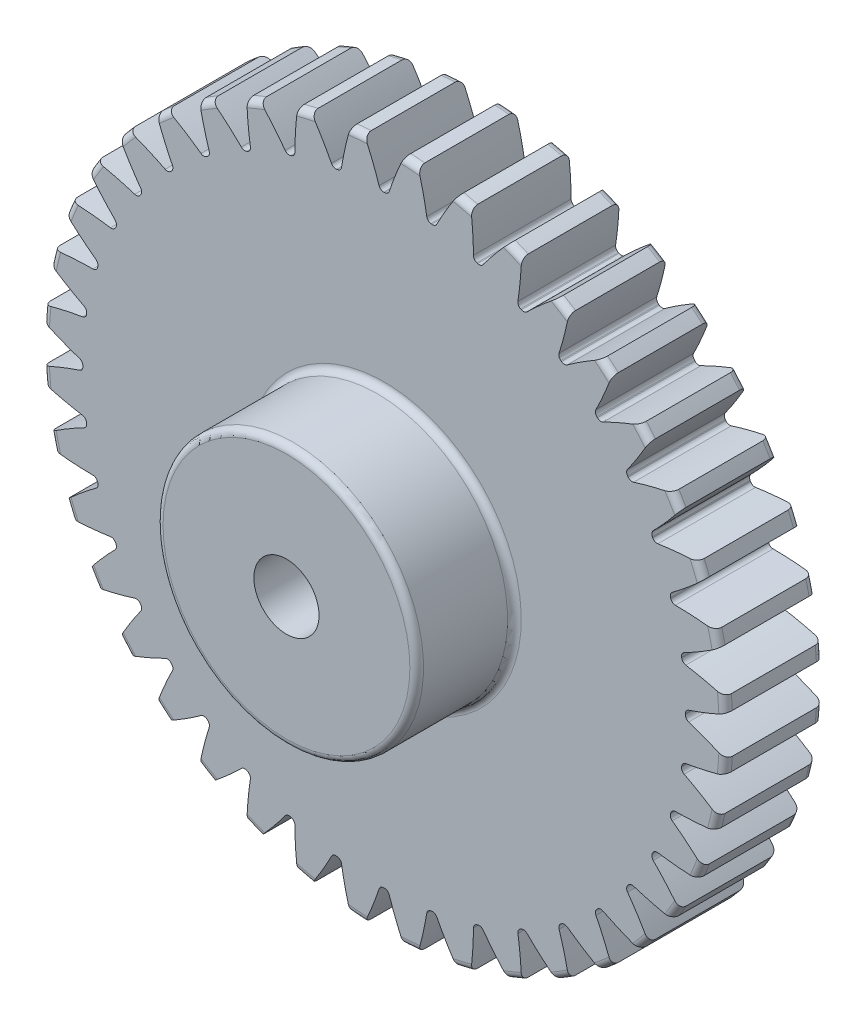
SolidWorks part; units mm, degrees
ref_plane "Front Plane" through (0, 0, 0) normal (0, 0, 1) x (1, 0, 0)
ref_plane "Top Plane" through (0, 0, 0) normal (0, 1, 0) x (1, 0, 0)
ref_plane "Right Plane" through (0, 0, 0) normal (1, 0, 0) x (0, 0, -1)
sketch "Sketch1" plane through (0, 0, 0) normal (0, 0, 1) x (1, 0, 0)
  line L0 (-508, 0) -> (508, 0) construction
  circle A0 centre (0, 0) radius 21 construction
  circle A1 centre (0, 0) radius 20 construction
  circle A2 centre (0, 0) radius 18.5 construction
  circle A3 centre (0, 0) radius 8 construction
  circle A4 centre (0, 0) radius 4 construction
  dimension "D2" = 1
  dimension "D3" = 2.5
  dimension "D1" = 2.5
sketch "Sketch2" plane through (0, 0, 0) normal (1, 0, 0) x (0, 0, -1)
  line L0 (0, 0) -> (-6, 0) construction
  line L1 (-6, 0) -> (-12, 0) construction
  dimension "Overall Width" = 12
  dimension "Face Width" = 6
sketch "Sketch4" plane through (0, 0, 0) normal (1, 0, 0) x (0, 0, -1)
  line L0 (-12, 4) -> (-12, 8)
  line L1 (-12, 8) -> (-6, 8)
  line L2 (-6, 8) -> (-6, 21)
  line L3 (-6, 21) -> (0, 21)
  line L4 (0, 21) -> (0, 4)
  line L5 (-6, 8) -> (-6, 0) construction
  line L6 (0, 21) -> (0, -21) construction
  line L7 (-6, 8) -> (0, 8) construction
  line L12 (-12, 4) -> (0, 4)
revolve "Revolve1" add sketch "Sketch4" angle 360 about L1
fillet "Fillet2" radius 0.42 4 edges at (0, 8, 12) (0, 8, 6) (0, 21, 6) (0, 21, 0)
sketch "Sketch7" plane through (0, 0, 6) normal (0, 0, 1) x (1, 0, 0)
  line L0 (0, 0) -> (0, 21) construction
  line L1 (0.7852, 19.9846) -> (1.1869, 20.9664) construction
  line L3 (1.6476, 20.9353) -> (1.5692, 19.9383) construction
  line L4 (1.5692, 19.9383) -> (1.4515, 18.443) construction
  line L5 (0, 0) -> (1.4515, 18.443) construction
  line L6 (0.7852, 19.9846) -> (0, 0) construction
  line L7 (0.7852, 19.9846) -> (0.8245, 20.9838) construction
  line L8 (0.7852, 19.9846) -> (0, 0) construction
  circle A0 centre (0, 0) radius 21 construction
  arc A1 (-0.027, 18.5) -> (0.027, 18.5) centre (0, 0) cw
  circle A2 centre (0, 0) radius 18.5 construction
  arc A3 (-0.7852, 19.9846) -> (0.7852, 19.9846) centre (0, 0) cw construction
  circle A4 centre (0, 0) radius 20 construction
  arc A5 (2.0774, 20.897) -> (1.2172, 20.9647) centre (0, 0) ccw construction
  arc A6 (0.7852, 19.9846) -> (2.3507, 19.8614) centre (0, 0) cw construction
  arc A7 (-1.2172, 20.9647) -> (1.2172, 20.9647) centre (0, 0) cw
  arc A8 (0.3122, 18.7056) -> (1.2172, 20.9647) centre (19.296, 12.4116) cw
  arc A9 (-0.3122, 18.7056) -> (-1.2172, 20.9647) centre (-19.296, 12.4116) ccw
  arc A10 (-0.027, 18.5) -> (-0.3122, 18.7056) centre (-0.0274, 18.8) cw
  arc A11 (0.027, 18.5) -> (0.3122, 18.7056) centre (0.0274, 18.8) ccw
  point P26 (-0.2447, 18.4984)
  point P29 (0.2447, 18.4984)
  dimension "D4" = 0.3
  dimension "D5" = 20
  dimension "D3" = 20
  dimension "D1" = 3.1416
  dimension "D2" = 1.5708
extrude "Cut-Extrude2" cut sketch "Sketch7" against normal through all
pattern_circular "CirPattern1" count 40 over 360 about axis through (0, 0, 12) along (0, 0, -1) of "Cut-Extrude2"
sketch "Sketch8" plane through (0, 0, 0) normal (0, 0, -1) x (-1, 0, 0)
  circle A0 centre (0, 0) radius 2
  circle A1 centre (0, 0) radius 4
  circle A2 centre (0, 0) radius 4 construction
  dimension "D1" = 4
extrude "Boss-Extrude1" add sketch "Sketch8" against normal up to surface (12 mm away) up to face at (0, -7.58, 12)
equation "\"D1@Sketch1\"=2.5*(\"Pitch Dia.@Sketch1\"/\"Number of Teeth@Sketch1\")"
equation "\"D1@CirPattern1\"=\"Number of Teeth@Sketch1\""
equation "\"D1@Fillet2\"=\"OD@Sketch1\"*.01"
equation "\"D1@Sketch7\"=3.14159*(\"Pitch Dia.@Sketch1\"/\"Number of Teeth@Sketch1\")"
equation "\"D2@Sketch7\"=\"D1@Sketch7\"/2"
equation "\"D4@Sketch7\"=\"D1@Sketch7\"*.0955"
equation "\"D5@Sketch7\"=\"Pitch Dia.@Sketch1\"/2"
